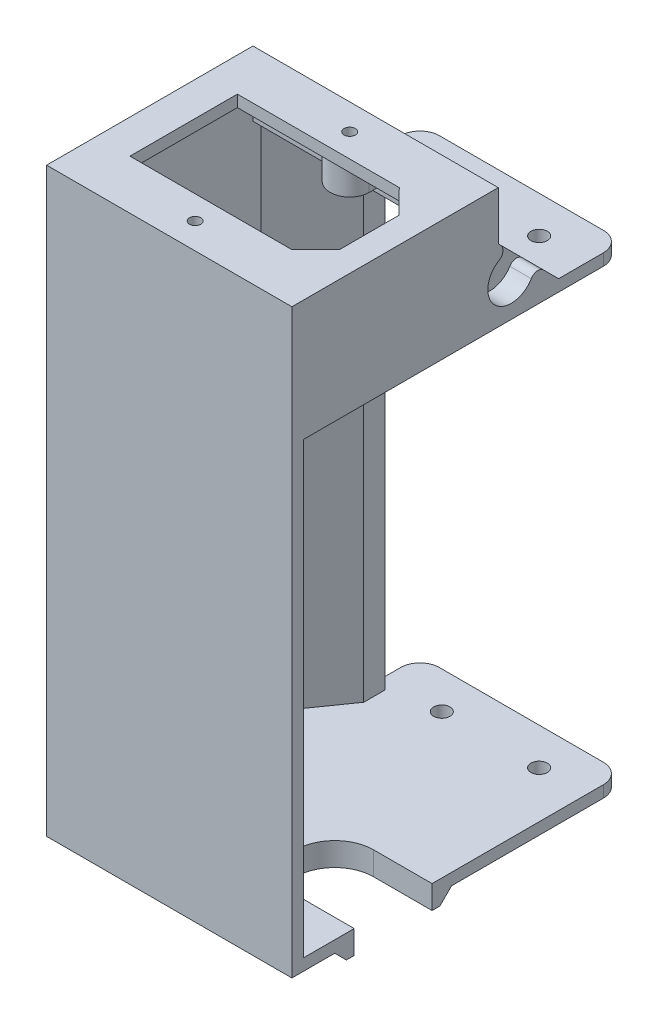
SolidWorks part; units mm, degrees
material "ABS"
ref_plane "Front Plane" through (0, 0, 0) normal (0, 0, 1) x (1, 0, 0)
ref_plane "Top Plane" through (0, 0, 0) normal (0, 1, 0) x (1, 0, 0)
ref_plane "Right Plane" through (0, 0, 0) normal (1, 0, 0) x (0, 0, -1)
sketch "Sketch1" plane through (0, 0, 0) normal (0, 1, 0) x (1, 0, 0)
  line L0 (-24.5, 11.5) -> (24.5, 11.5) construction
  line L1 (-24.5, -21) -> (24.5, -21) construction
  line L2 (-24.5, -21) -> (-24.5, 21) construction
  line L3 (-24.5, 21) -> (24.5, 21) construction
  line L4 (24.5, -21) -> (24.5, 21) construction
  line L5 (-24.5, -21) -> (24.5, 21) construction
  line L6 (-24.5, 21) -> (24.5, -21) construction
  line L7 (0, 21) -> (0, -21) construction
  line L8 (24.5, -64) -> (-24.5, -64) construction
  line L9 (-24.5, -2.5) -> (-1, -2.5) construction
  line L10 (-1, -2.5) -> (-1, -21) construction
  circle A0 centre (12.5, 11.5) radius 2.1 construction
  circle A1 centre (-12.5, 11.5) radius 2.1 construction
  point P0 (0, 0)
  dimension "D4" = 25
  dimension "D5" = 4.2
  dimension "D1" = 49
  dimension "D2" = 42
  dimension "D3" = 32.5
  dimension "D6" = 43
  dimension "D7" = 18.5
  dimension "D8" = 23.5
sketch "Sketch2" plane through (0, 0, 0) normal (0, 1, 0) x (1, 0, 0)
  line L0 (24.5, 21) -> (-27.6, 21)
  line L1 (-27.6, 21) -> (-27.6, 4.5)
  line L3 (-27.6, 4.5) -> (-38.5, -11)
  line L4 (-38.5, -11) -> (-38.5, -64)
  line L5 (-38.5, -64) -> (24.5, -64)
  line L6 (24.5, -64) -> (24.5, 21)
  line L8 (-38.5, -11) -> (24.5, -11)
  line L9 (-24.5, -2.5) -> (-1, -2.5) construction
  line L10 (-24.5, -21) -> (-24.5, 21) construction
  dimension "D1" = 63
  dimension "D2" = 7
  dimension "D3" = 3.1
  dimension "D4" = 53
extrude "Boss-Extrude1" add sketch "Sketch2" along normal blind 121.3 contours L3 L8 L6 L0 L1 | L8 L4 L5 L6 region at (-2.9815, 0, -4.4776) region at (-7, 0, 37.5)
extrude "Boss-Extrude2" add sketch "Sketch2<3>" along normal blind 28 from surface contours L8 L4 L5 L6 region at (-7, 0, 37.5) starting at face at (-13.8667, 121.3, 15.4167)
sketch "Sketch2<3>" plane through (0, 0, 0) normal (0, 1, 0) x (1, 0, 0) same geometry as "Sketch2"
chamfer "Chamfer5" distance 15.5 angle 45 1 edges
sketch "Sketch7" plane through (24.5, 0, 0) normal (1, 0, 0) x (0, 0, -1)
  circle A0 centre (-7.675, 127.9) radius 6
  dimension "D1" = 12
extrude "Cut-Extrude3" cut sketch "Sketch7" against normal blind 5.5
fillet "Fillet5" radius 2 2 edges at (21.75, 127.4891, 1.6891) (21.75, 133.8859, 8.0859)
shell "Shell2" thickness 3 removed face at (24.5, 108.9893, 12.6744)
sketch "Sketch4" plane through (24.5, 0, 0) normal (1, 0, 0) x (0, 0, -1)
  line L0 (21, 118.3) -> (9, 118.3)
  line L1 (3.2574, 118.3) -> (18, 118.3) construction
  line L2 (9, 118.3) -> (9, 3)
  line L3 (-61, 3) -> (18, 3) construction
  line L4 (9, 3) -> (21, 3)
  line L5 (21, 121.3) -> (21, 0) construction
  line L6 (21, 118.3) -> (21, 3)
  dimension "D1" = 12
extrude "Cut-Extrude1" cut sketch "Sketch4" against normal through all
sketch "Sketch5" plane through (24.5, 0, 0) normal (1, 0, 0) x (0, 0, -1)
  line L0 (3.2574, 118.3) -> (-61, 118.3)
  line L1 (-61, 118.3) -> (-61, 146.3)
  line L2 (-61, 146.3) -> (-14, 146.3)
  line L3 (-14, 146.3) -> (-14, 135.5574)
  line L4 (-13.3378, 134.8952) -> (-14, 135.5574) construction
  line L5 (-61, 146.3) -> (-61, 3) construction
  line L6 (3.2574, 118.3) -> (-0.6798, 122.2372) construction
  line L7 (-13.3378, 134.8952) -> (-14, 135.5574)
  line L8 (3.2574, 118.3) -> (-0.6798, 122.2372)
  arc A0 (-13.3378, 134.8952) -> (-0.6798, 122.2372) centre (-7.675, 127.9) ccw construction
  arc A1 (-13.3378, 134.8952) -> (-0.6798, 122.2372) centre (-7.675, 127.9) ccw
extrude "Boss-Extrude5" add sketch "Sketch5" against normal blind 3
sketch "Sketch6" plane through (0, 0, 0) normal (0, -1, 0) x (1, 0, 0)
  circle A0 centre (-12.5, -11.5) radius 2.1
  circle A1 centre (12.5, -11.5) radius 2.1
  circle A2 centre (-12.5, -11.5) radius 2.1 construction
  circle A3 centre (12.5, -11.5) radius 2.1 construction
extrude "Cut-Extrude2" cut sketch "Sketch6" against normal up to surface (121.3 mm away) up to face at (-1.55, 121.3, -10.6875)
sketch "Sketch8" plane through (0, 146.3, 0) normal (0, -1, 0) x (1, 0, 0)
  line L0 (-29.5, 51) -> (-29.5, 24) construction
  line L1 (-29.5, 24) -> (11.65, 24) construction
  line L2 (11.65, 24) -> (17.6, 30) construction
  line L3 (17.6, 30) -> (17.6, 45) construction
  line L4 (17.6, 45) -> (11.65, 51) construction
  line L5 (11.65, 51) -> (-29.5, 51) construction
  line L6 (-29.8, 51.3) -> (-29.8, 23.7)
  line L7 (-29.8, 23.7) -> (11.775, 23.7)
  line L8 (11.775, 23.7) -> (17.9, 29.8765)
  line L9 (17.9, 29.8765) -> (17.9, 45.1235)
  line L10 (17.9, 45.1235) -> (11.775, 51.3)
  line L11 (11.775, 51.3) -> (-29.8, 51.3)
  line L12 (-12, 57.35) -> (-12, 61)
  line L13 (-35.5, 61) -> (24.5, 61) construction
  line L14 (-2, 57.35) -> (-2, 61)
  line L15 (-2, 61) -> (-12, 61)
  line L16 (-12, 17.65) -> (-12, 14)
  line L17 (21.5, 14) -> (-35.5, 14) construction
  line L18 (-2, 17.65) -> (-2, 14)
  line L19 (-2, 14) -> (-12, 14)
  arc A0 (-12, 57.35) -> (-2, 57.35) centre (-7, 57.35) ccw
  arc A1 (-2, 17.65) -> (-12, 17.65) centre (-7, 17.65) ccw
  circle A2 centre (-7, 17.65) radius 1.45
  circle A3 centre (-7, 57.35) radius 1.45
  line M1 (-35.5, 14) -> (21.5, 14)
  line M3 (21.5, 61) -> (-35.5, 61)
  dimension "D2" = 10
  dimension "D3" = 2.9
  dimension "D1" = 0.3
extrude "Cut-Extrude4" cut sketch "Sketch8" against normal up to surface (3 mm away) contours L10 L11 L6 L7 L8 L9 | A2 | A3 region at (-6.5952, 146.3, 37.5) region at (-7, 146.3, 17.65) region at (-7, 146.3, 57.35) up to face at (-7, 149.3, 37.5)
extrude "Boss-Extrude6" add sketch "Sketch8<3>" along normal blind 8 contours L12 A0 L14 A3 M3 | L18 A1 L16 A2 M1 region at (-11.8678, 146.3, 59.175) region at (-7, 146.3, 22.5178)
sketch "Sketch8<3>" plane through (0, 146.3, 0) normal (0, -1, 0) x (1, 0, 0) same geometry as "Sketch8"
sketch "Sketch9" plane through (0, 0, 0) normal (0, -1, 0) x (1, 0, 0)
  line L0 (9.5, 48) -> (24.5, 48)
  line L1 (24.5, 64) -> (24.5, -21) construction
  line L2 (24.5, 48) -> (24.5, 28)
  line L3 (24.5, 28) -> (9.5, 28)
  line L4 (-38.5, 64) -> (24.5, 64) construction
  line L5 (24.5, 26) -> (9.5, 26)
  line L6 (9.5, 50) -> (24.5, 50)
  line L7 (24.5, 26) -> (24.5, 28)
  line L8 (24.5, 48) -> (24.5, 50)
  arc A0 (9.5, 48) -> (9.5, 28) centre (9.5, 38) ccw
  arc A1 (9.5, 50) -> (9.5, 26) centre (9.5, 38) ccw
  line M6 (24.5, -21) -> (24.5, 64)
  dimension "D1" = 20
  dimension "D2" = 26
  dimension "D3" = 15
  dimension "D4" = 2
extrude "Cut-Extrude5" cut sketch "Sketch9" against normal up to surface (3 mm away) contours L0 A0 L3 M6 region at (12.964, 0, 38)
extrude "Boss-Extrude7" add sketch "Sketch9<4>" along normal blind 3 contours L6 A1 L5 L3 A0 L0 M6 region at (-0.8612, 0, 38)
sketch "Sketch9<4>" plane through (0, 0, 0) normal (0, -1, 0) x (1, 0, 0) same geometry as "Sketch9"
chamfer "Chamfer7" distance 3 angle 45 3 edges at (-2.5, 0, 38)
fillet "Fillet6" radius 5 4 edges at (24.5, 1.5, -21) (24.5, 119.8, -21) (-27.6, 1.5, -21) (-27.6, 119.8, -21)
